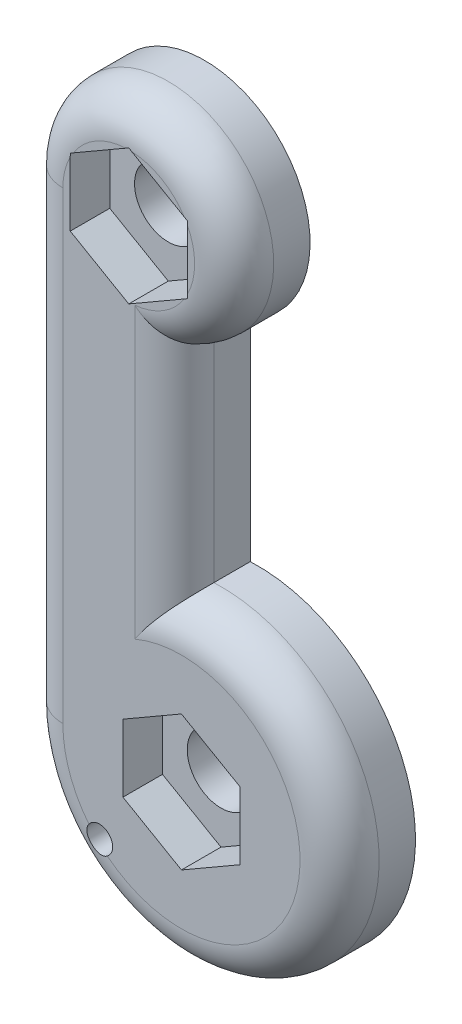
SolidWorks part; units mm, degrees
ref_plane "Front Plane" through (0, 0, 0) normal (0, 0, 1) x (1, 0, 0)
ref_plane "Top Plane" through (0, 0, 0) normal (0, 1, 0) x (1, 0, 0)
ref_plane "Right Plane" through (0, 0, 0) normal (1, 0, 0) x (0, 0, -1)
sketch "Sketch1" plane through (0, 0, 0) normal (0, 0, 1) x (1, 0, 0)
  line L0 (-7.5, 22) -> (-7.5, 0)
  line L2 (-0.3362, 7.4925) -> (-0.3362, 17.4925)
  circle A0 centre (0, 0) radius 1.6
  arc A1 (-7.5, 0) -> (-0.3362, 7.4925) centre (0, 0) ccw
  circle A2 centre (-2.5, 22) radius 1.6
  arc A3 (-0.3362, 17.4925) -> (-7.5, 22) centre (-2.5, 22) ccw
  dimension "D2" = 10
  dimension "D3" = 3.2
  dimension "D4" = 15
  dimension "D5" = 10
  dimension "D6" = 22
extrude "Boss-Extrude1" add sketch "Sketch1" along normal blind 3.6
sketch "Sketch2" plane through (0, 0, 3.6) normal (0, 0, 1) x (1, 0, 0)
  line L0 (0, 0) -> (-3.8891, -3.8891) construction
  line L1 (-7.5, 22) -> (-7.5, 0) construction
  circle A0 centre (-3.8891, -3.8891) radius 0.625
  dimension "D2" = 1.25
  dimension "D1" = 5.5
  dimension "D3" = 3.6109
extrude "Cut-Extrude1" cut sketch "Sketch2" against normal through all
sketch "Sketch3" plane through (0, 0, 3.6) normal (0, 0, 1) x (1, 0, 0)
  line L1 (0, 3.2043) -> (-2.775, 1.6021)
  line L2 (-2.775, 1.6021) -> (-2.775, -1.6021)
  line L3 (-2.775, -1.6021) -> (0, -3.2043)
  line L4 (0, -3.2043) -> (2.775, -1.6021)
  line L5 (2.775, -1.6021) -> (2.775, 1.6021)
  line L6 (2.775, 1.6021) -> (0, 3.2043)
  line L7 (-2.5, 18.7957) -> (0.275, 20.3979)
  line L8 (0.275, 20.3979) -> (0.275, 23.6021)
  line L9 (0.275, 23.6021) -> (-2.5, 25.2043)
  line L10 (-2.5, 25.2043) -> (-5.275, 23.6021)
  line L11 (-5.275, 23.6021) -> (-5.275, 20.3979)
  line L12 (-5.275, 20.3979) -> (-2.5, 18.7957)
  circle A0 centre (0, 0) radius 2.775 construction
  circle A1 centre (-2.5, 22) radius 2.775 construction
  dimension "D1" = 5.55
extrude "Cut-Extrude2" cut sketch "Sketch3" against normal blind 1.875
sketch "Sketch4" [suppressed] plane through (0, 0, 0) normal (0, 0, -1) x (-1, 0, 0)
  circle A0 centre (0, 0) radius 2.775
  circle A1 centre (2.5, 22) radius 2.775
  dimension "D1" = 5.55
extrude "Cut-Extrude3" [suppressed] cut sketch "Sketch4" against normal blind 1.875
fillet "Fillet1" radius 1.875 4 edges at (0.1628, 26.232, 3.6) (5.4209, -5.1831, 3.6) (-0.3362, 12.4925, 3.6) (-7.5, 11, 3.6)
fillet "Fillet2" [suppressed] radius 1.875
